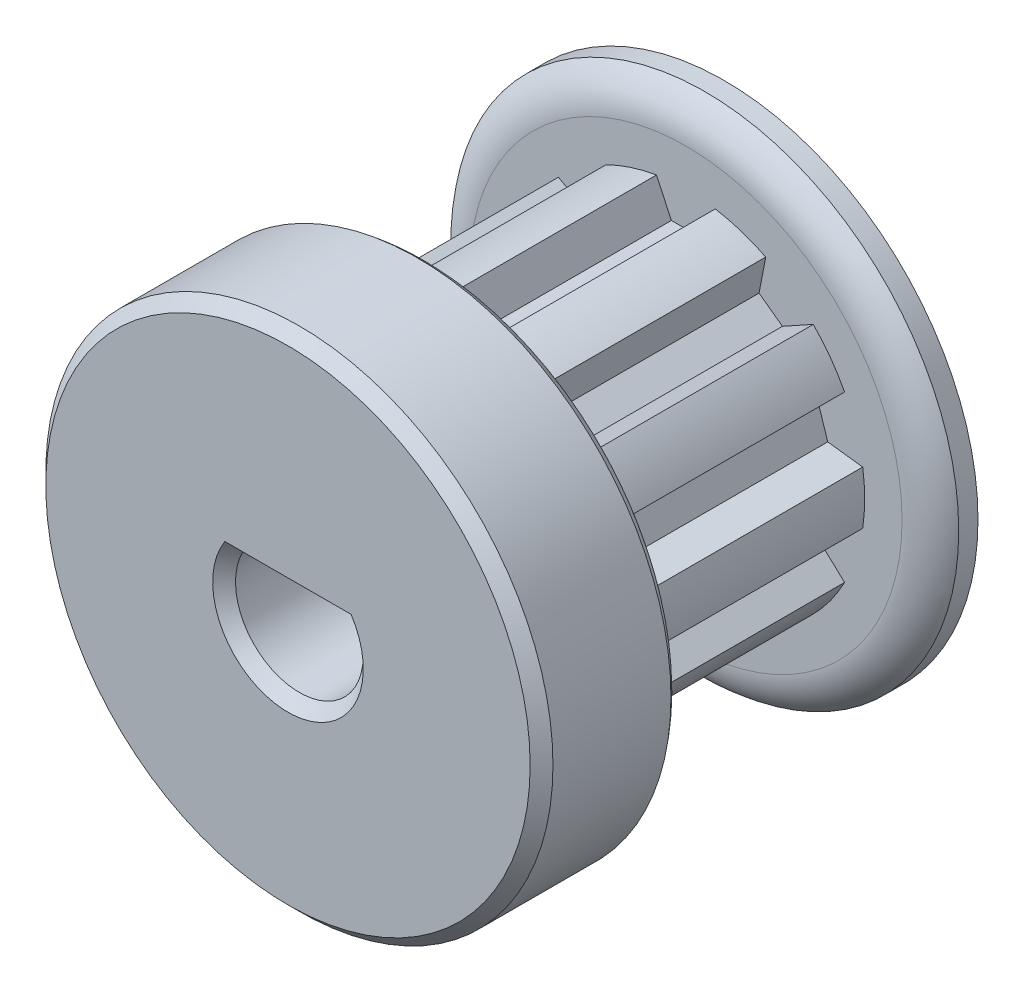
SolidWorks part; units mm, degrees
ref_plane "Front Plane" through (0, 0, 0) normal (0, 0, 1) x (1, 0, 0)
ref_plane "Top Plane" through (0, 0, 0) normal (0, 1, 0) x (1, 0, 0)
ref_plane "Right Plane" through (0, 0, 0) normal (1, 0, 0) x (0, 0, -1)
sketch "Sketch1" plane through (0, 0, 0) normal (0, 0, 1) x (1, 0, 0)
  line L0 (-1.2878, 7.7293) -> (-0.635, 6.3293)
  line L1 (-0.635, 6.3293) -> (0.635, 6.3293)
  line L2 (0.635, 6.3293) -> (1.2878, 7.7293)
  line L3 (-1.2878, 7.7293) -> (1.2878, 7.7293)
  line L4 (0, 0) -> (0, 6.3293) construction
  line L5 (0, 6.3293) -> (0, 8.6153) construction
  circle A0 centre (0, 0) radius 8.0899 construction
  circle A1 centre (0, 0) radius 11.1125 construction
  circle A2 centre (0, 0) radius 7.8359 construction
  point P6 (0, 7.7293)
  point P11 (0, 8.0899)
  point P13 (0, 11.1125)
  point P14 (0, 7.8359)
  dimension "D1" = 1.4
  dimension "PD" = 16.1798
  dimension "OD" = 22.225
  dimension "D3" = 1.27
  dimension "Gear OD" = 15.6718
  dimension "b" = 50
  dimension "hs" = 2.286
sketch "Sketch2" plane through (0, 0, 0) normal (1, 0, 0) x (0, 0, -1)
  line L0 (-3.9878, 2.5) -> (10.3124, 2.5)
  line L4 (-3.9878, 11.1125) -> (-2.2987, 11.1125) construction
  line L5 (-2.2987, 11.1125) -> (-2.2987, 7.8359) construction
  line L6 (-2.2987, 7.8359) -> (8.6233, 7.8359)
  line L7 (8.6233, 7.8359) -> (8.6233, 11.1125) construction
  line L8 (8.6233, 11.1125) -> (10.3124, 11.1125) construction
  line L9 (10.3124, 11.1125) -> (10.3124, 2.5)
  line L10 (-10.3124, 0) -> (10.3124, 0) construction
  line L11 (-3.9878, 2.5) -> (-3.9878, 11.1125)
  line L13 (-3.9878, 11.1125) -> (-3.1432, 11.1125)
  line L14 (-2.2987, 9.4742) -> (-2.2987, 7.8359)
  line L15 (8.6233, 7.8359) -> (8.6233, 9.4742)
  line L16 (9.4679, 11.1125) -> (10.3124, 11.1125)
  arc A0 (-2.2987, 9.4742) -> (-3.1432, 11.1125) centre (-4.31, 9.4742) ccw
  arc A1 (8.6233, 9.4742) -> (9.4679, 11.1125) centre (10.6346, 9.4742) cw
  point P12 (-2.2987, 9.4742)
  point P14 (-3.1432, 11.1125)
  point P20 (8.6233, 9.4742)
  point P21 (9.4679, 11.1125)
  point P25 (8.6233, 0)
  point P26 (-2.2987, 0)
  dimension "D1" = 14.3002
  dimension "OA" = 20.6248
  dimension "Bore" = 5
  dimension "Inside Width" = 10.922
revolve "Revolve1" add sketch "Sketch2" angle 360 mid plane about L10
sketch "Sketch3" plane through (0, 0, 0) normal (0, 0, 1) x (1, 0, 0)
  line L0 (-0.635, 6.3293) -> (0.635, 6.3293) construction
  line L1 (0.635, 6.3293) -> (1.2878, 7.7293) construction
  line L2 (-1.2878, 7.7293) -> (-0.635, 6.3293) construction
  line L3 (-0.635, 6.3293) -> (0.635, 6.3293)
  line L4 (0.635, 6.3293) -> (1.2878, 7.7293)
  line L5 (-1.2878, 7.7293) -> (-0.635, 6.3293)
  circle A0 centre (0, 0) radius 7.8359 construction
  arc A1 (1.2878, 7.7293) -> (-1.2878, 7.7293) centre (0, 0) ccw
extrude "Cut-Extrude1" cut sketch "Sketch3" against normal up to vertex (8.6233 mm away) from vertex up to point (0, 7.8359, -8.6233) starting at point (0, 7.8359, 2.2987)
fillet "Fillet1" [suppressed] radius 0.61
pattern_circular "CirPattern1" count 10 over 360 about axis through (0, 0, 10.3124) along (0, 0, 1) of "Cut-Extrude1", "Fillet1"
ref_plane "Contact Plane 2" through (0, 0, -10.3124) normal (0, 0, -1) x (-1, 0, 0)
ref_axis "Center Axis 1" through (0, 0, -10.3124) along (0, 0, 1)
sketch "Sketch5" plane through (0, 0, 3.9878) normal (0, 0, 1) x (1, 0, 0)
  line L0 (2.2913, 1) -> (-2.2913, 1)
  line L1 (0, -2.5) -> (0, 1) construction
  line L2 (0, 1) -> (0, 2.5) construction
  arc A0 (2.2913, 1) -> (-2.2913, 1) centre (0, 0) ccw
  circle M4 centre (0, 0) radius 2.5
  dimension "D2" = 5
  dimension "D1" = 1.5
extrude "Boss-Extrude1" add sketch "Sketch5" against normal blind 7.62 contours L0 M4 region at (0, 1.6187, 3.9878)
sketch "Sketch6" plane through (0, 0, -10.3124) normal (0, 0, -1) x (-1, 0, 0)
  line L1 (5.6725, 0) -> (2.8362, 4.9125)
  line L2 (2.8362, 4.9125) -> (-2.8362, 4.9125)
  line L3 (-2.8362, 4.9125) -> (-5.6725, 0)
  line L4 (-5.6725, 0) -> (-2.8362, -4.9125)
  line L5 (-2.8362, -4.9125) -> (2.8362, -4.9125)
  line L6 (2.8362, -4.9125) -> (5.6725, 0)
  circle A0 centre (0, 0) radius 4.9125 construction
  dimension "D1" = 9.825
extrude "Cut-Extrude2" cut sketch "Sketch6" against normal up to surface (6.6802 mm away) up to face at (0, 1.75, -3.6322)
sketch "Sketch8" plane through (0, 0, 3.9878) normal (0, 0, 1) x (1, 0, 0)
  line L0 (2.2913, 1) -> (-2.2913, 1) construction
  line L1 (2.2913, 1) -> (-2.2913, 1)
  arc A0 (-2.2913, 1) -> (2.2913, 1) centre (0, 0) ccw construction
  circle A1 centre (0, 0) radius 11.1125
  circle A2 centre (0, 0) radius 11.1125
  arc A3 (-2.2913, 1) -> (2.2913, 1) centre (0, 0) ccw
  dimension "D1" = 0
extrude "Boss-Extrude2" add sketch "Sketch8" along normal blind 4.826
sketch "Sketch12" plane through (0, 0, 8.8138) normal (0, 0, 1) x (1, 0, 0)
  line L3 (2.4799, 1.3) -> (-2.4799, 1.3)
  line L4 (2.4799, 1.3) -> (-2.4799, 1.3)
  arc A2 (-2.4799, 1.3) -> (2.4799, 1.3) centre (0, 0) ccw
  arc A3 (-2.4799, 1.3) -> (2.4799, 1.3) centre (0, 0) ccw
  dimension "D1" = 0.3
extrude "Cut-Extrude3" cut sketch "Sketch12" against normal blind 24.384
chamfer "Chamfer2" distance 0.5 angle 45 3 edges at (11.1125, 0, 8.8138) (0, 1.3, 8.8138) (0, -2.8, 8.8138)
